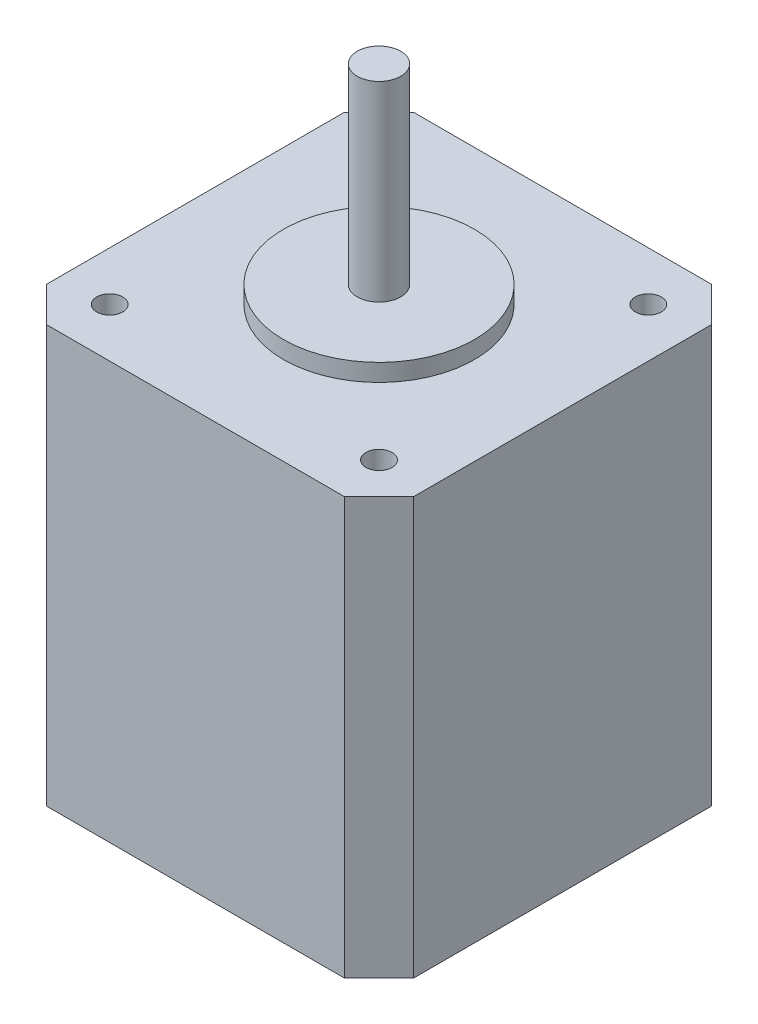
SolidWorks part; units mm, degrees
ref_plane "Front Plane" through (0, 0, 0) normal (0, 0, 1) x (1, 0, 0)
ref_plane "Top Plane" through (0, 0, 0) normal (0, 1, 0) x (1, 0, 0)
ref_plane "Right Plane" through (0, 0, 0) normal (1, 0, 0) x (0, 0, -1)
sketch "Sketch1" plane through (0, 0, 0) normal (0, 1, 0) x (1, 0, 0)
  line L1 (-21.15, -21.15) -> (21.15, -21.15)
  line L2 (-21.15, -21.15) -> (-21.15, 21.15)
  line L3 (-21.15, 21.15) -> (21.15, 21.15)
  line L4 (21.15, -21.15) -> (21.15, 21.15)
  line L5 (-21.15, -21.15) -> (21.15, 21.15) construction
  line L6 (-21.15, 21.15) -> (21.15, -21.15) construction
  point P0 (0, 0)
  dimension "D1" = 42.3
  dimension "D2" = 42.3
extrude "Boss-Extrude1" add sketch "Sketch1" along normal blind 48
sketch "Sketch2" plane through (0, 48, 0) normal (0, 1, 0) x (1, 0, 0)
  line L0 (0, 0) -> (0, 21.15) construction
  line L1 (21.15, 21.15) -> (-21.15, 21.15) construction
  line L2 (21.15, 0) -> (-21.15, 0) construction
  line L3 (21.15, -21.15) -> (21.15, 21.15) construction
  line L4 (-21.15, 21.15) -> (-21.15, -21.15) construction
  line L5 (0, 0) -> (0, -21.15) construction
  line L6 (-21.15, -21.15) -> (21.15, -21.15) construction
  line L7 (-21.15, 17.15) -> (-17.15, 21.15)
  line L8 (21.15, 17.15) -> (17.15, 21.15)
  line L9 (-21.15, -17.15) -> (-17.15, -21.15)
  line L10 (21.15, -17.15) -> (17.15, -21.15)
  circle A0 centre (-15.5, 15.5) radius 1.5
  circle A2 centre (15.5, 15.5) radius 1.5
  circle A3 centre (15.5, -15.5) radius 1.5
  circle A4 centre (-15.5, -15.5) radius 1.5
  circle A5 centre (0, 0) radius 11
  circle A6 centre (0, 0) radius 2.5
  line M1 (21.15, -21.15) -> (21.15, 21.15)
  line M2 (21.15, 21.15) -> (-21.15, 21.15)
  line M3 (-21.15, 21.15) -> (-21.15, -21.15)
  line M4 (-21.15, -21.15) -> (21.15, -21.15)
  dimension "D1" = 3
  dimension "D2" = 5.65
  dimension "D3" = 5.65
  dimension "D4" = 22
  dimension "D5" = 5
  dimension "D6" = 4
  dimension "D7" = 4
extrude "Cut-Extrude1" cut sketch "Sketch2" against normal through all contours L7 M3 M2 | L8 M1 M2 | L10 M1 M4 | L9 M3 M4 region at (-19.8167, 48, -19.8167) region at (-19.8167, 48, 19.8167) region at (19.8167, 48, -19.8167) region at (19.8167, 48, 19.8167)
extrude "Cut-Extrude2" cut sketch "Sketch2<3>" against normal blind 4.5 contours A2 | A3 | A4 | A0 region at (15.5, 48, -15.5) region at (15.5, 48, 15.5) region at (-15.5, 48, 15.5)
sketch "Sketch2<3>" plane through (0, 48, 0) normal (0, 1, 0) x (1, 0, 0) same geometry as "Sketch2"
extrude "Boss-Extrude2" add sketch "Sketch2<4>" along normal blind 2 contours A5
sketch "Sketch2<4>" plane through (0, 48, 0) normal (0, 1, 0) x (1, 0, 0) same geometry as "Sketch2"
extrude "Boss-Extrude3" add sketch "Sketch2<5>" along normal blind 24 contours A6
sketch "Sketch2<5>" plane through (0, 48, 0) normal (0, 1, 0) x (1, 0, 0) same geometry as "Sketch2"
